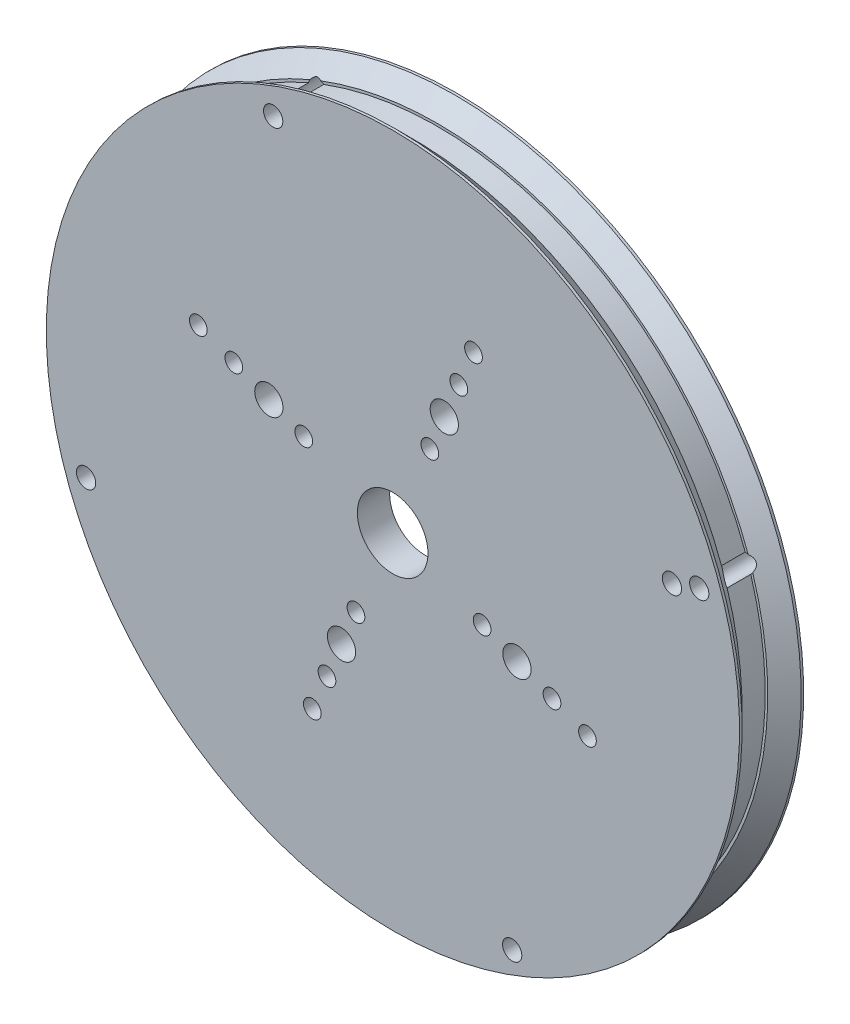
SolidWorks part; units mm, degrees
ref_plane "Plan de face" through (0, 0, 0) normal (0, 0, 1) x (1, 0, 0)
ref_plane "Plan de dessus" through (0, 0, 0) normal (0, 1, 0) x (1, 0, 0)
ref_plane "Plan de droite" through (0, 0, 0) normal (1, 0, 0) x (0, 0, -1)
sketch "Esquisse1" plane through (0, 0, 1.6866) normal (1, 0, 0) x (0, 0, -1)
  line L1 (0.1714, -3) -> (-1.8286, -3)
  line L2 (0.1714, -3) -> (0.1714, 22.5)
  line L3 (0.1714, 22.5) -> (-1.8286, 22.5)
  line L4 (-1.8286, -3) -> (-1.8286, 22.5)
  line L13 (1.6714, -3) -> (0.1714, -3)
  line L14 (1.6714, -3) -> (1.6714, 24)
  line L15 (1.6714, 24) -> (0.1714, 24)
  line L16 (0.1714, -3) -> (0.1714, 24)
  line L17 (-1.8286, 24) -> (-3.3286, 24)
  line L18 (-1.8286, 24) -> (-1.8286, -3)
  line L19 (-1.8286, -3) -> (-3.3286, -3)
  line L20 (-3.3286, 24) -> (-3.3286, -3)
  dimension "D1" = 1.5
  dimension "D2" = 1.5
  dimension "D3" = 2
  dimension "D4" = 25.5
  dimension "D5" = 27
revolve "Révolution1" add sketch "Esquisse1" angle 360 about L1 region at (0, 9.75, 2.5152) region at (0, 10.5, 0.7652) region at (0, 10.5, 4.2652)
sketch "Esquisse2" plane through (0, 0, 5.0152) normal (0, 0, 1) x (1, 0, 0)
  line L0 (26.9976, -3.3576) -> (-27, -2.9934) construction
  circle A0 centre (-0.0182, -3.1754) radius 2.75
  circle A1 centre (0, -3) radius 27 construction
extrude "Enlèv. mat.-Extru.1" cut sketch "Esquisse2" against normal blind 10
sketch "Esquisse13" plane through (0, 0, 0) normal (0, 0, 1) x (1, 0, 0)
  line L0 (-122.2352, 39.9508) -> (-38.6976, 41.258) construction
  line L1 (-36.0992, -44.5996) -> (67.3726, -4.8805) construction
  line L4 (15.1562, -9.278) -> (-15.1562, 3.278) construction
  line L5 (-6.278, -18.1562) -> (6.278, 12.1562) construction
  circle A2 centre (-2.8778, -9.9476) radius 0.6896
  circle A3 centre (6.9476, -5.8778) radius 0.6896
  circle A4 centre (9.6638, -7.0029) radius 1.1
  circle A5 centre (12.3938, -8.1338) radius 0.6896
  circle A6 centre (15.1562, -9.278) radius 0.6896
  circle A7 centre (2.8778, 3.9476) radius 0.6896
  circle A8 centre (4.0029, 6.6638) radius 1.1
  circle A9 centre (5.1338, 9.3938) radius 0.6896
  circle A10 centre (6.278, 12.1562) radius 0.6896
  circle A11 centre (-4.0029, -12.6638) radius 1.1
  circle A12 centre (-5.1338, -15.3938) radius 0.6896
  circle A13 centre (-6.278, -18.1562) radius 0.6896
  circle A14 centre (-6.9476, -0.1222) radius 0.6896
  circle A15 centre (-9.6638, 1.0029) radius 1.1
  circle A16 centre (-12.3938, 2.1338) radius 0.6896
  circle A17 centre (-15.1562, 3.278) radius 0.6896
  circle A19 centre (0, -3) radius 7.52 construction
  circle A20 centre (0, -3) radius 10.46 construction
  circle A21 centre (0, -3) radius 13.415 construction
  circle A22 centre (0, -3) radius 16.405 construction
sketch "Esquisse14" plane through (0, 0, 0) normal (0, 0, 1) x (1, 0, 0)
  line L0 (-122.2352, 39.9508) -> (-38.6976, 41.258) construction
  line L1 (-36.0992, -44.5996) -> (67.3726, -4.8805) construction
  spline S0 degree 2 poles (6.7095, 2.7436) (4.5975, -1.3195) (9.1051, -2.6286) knots 0 0 0 1 1 1 construction
  spline S1 degree 3 poles (-0.5608, 5.6062) (1.1805, 8.2527) (2.8687, 10.4384) (5.1281, 13.8669) (7.0874, 14.3139) (8.3916, 12.6802) (7.2661, 8.5047) (7.0552, 4.6338) (6.7095, 2.7436) knots 0 0 0 0 0.368171 0.418118 0.499474 0.581227 0.63128 1 1 1 1 construction
  spline S2 degree 2 poles (-0.5608, 5.6062) (-1.8662, 1.4438) (-5.8382, 3.5619) knots 0 0 0 1 1 1 construction
  spline S3 degree 3 poles (9.1051, -2.6286) (11.376, -4.297) (13.9367, -6.0338) (16.9471, -8.1818) (17.3829, -10.0409) (15.6763, -11.2158) (11.6017, -10.1948) (8.3971, -9.8909) (5.7682, -9.4912) knots 0 0 0 0 0.365231 0.41369 0.484595 0.573039 0.62458 1 1 1 1 construction
  spline S4 degree 2 poles (5.7682, -9.4912) (2.1673, -7.506) (0.914, -11.3287) knots 0 0 0 1 1 1 construction
  spline S5 degree 3 poles (0.914, -11.3287) (-1.3562, -14.5677) (-2.4297, -16.1534) (-4.9925, -19.7972) (-7.106, -20.4883) (-8.0922, -18.5459) (-7.4183, -14.316) (-7.0267, -12.3758) (-6.3958, -8.7367) knots 0 0 0 0 0.370191 0.421117 0.509255 0.593778 0.642852 1 1 1 1 construction
  spline S6 degree 2 poles (-6.3958, -8.7367) (-4.4116, -4.9383) (-8.4827, -3.685) knots 0 0 0 1 1 1 construction
  spline S7 degree 3 poles (-8.4827, -3.685) (-11.9491, -1.3363) (-13.5133, -0.3098) (-16.9826, 2.3011) (-16.9406, 4.3561) (-15.2444, 5.1901) (-10.9497, 4.5175) (-8.5569, 4.0332) (-5.8382, 3.5619) knots 0 0 0 0 0.388588 0.439956 0.513686 0.605056 0.653688 1 1 1 1 construction
  spline S8 degree 1 poles (-0.8345, 5.7361) (-5.7395, 3.8493) knots 0 0 1 1 construction
  spline S9 degree 1 poles (-8.6139, -3.9586) (-5.7395, 3.8493) knots 0 0 1 1 construction
  spline S10 degree 1 poles (-6.6834, -8.6393) (-8.6139, -3.9586) knots 0 0 1 1 construction
  spline S11 degree 1 poles (1.1852, -11.4645) (-6.6834, -8.6393) knots 0 0 1 1 construction
  spline S12 degree 1 poles (5.6702, -9.7797) (1.1852, -11.4645) knots 0 0 1 1 construction
  spline S13 degree 1 poles (9.2399, -2.3554) (5.6702, -9.7797) knots 0 0 1 1 construction
  spline S14 degree 1 poles (6.9965, 2.6453) (9.2399, -2.3554) knots 0 0 1 1 construction
  spline S15 degree 1 poles (-0.8345, 5.7361) (6.9965, 2.6453) knots 0 0 1 1 construction
  spline S16 degree 2 poles (-0.8345, 5.7361) (-1.3236, 4.2068) (-2.6043, 3.2067) (-4.2666, 3.072) (-5.7395, 3.8493) knots -0.004811 -0.004811 -0.004811 0.373998 0.626538 1.005348 1.005348 1.005348
  spline S17 degree 3 poles (-5.7395, 3.8493) (-6.2151, 3.9317) (-7.1851, 4.1035) (-8.5214, 4.3474) (-9.8525, 4.5913) (-11.2133, 4.8349) (-12.4217, 5.0437) (-13.4517, 5.2099) (-14.2791, 5.3495) (-15.1763, 5.3548) (-16.0151, 5.0974) (-16.7156, 4.5962) (-17.1548, 3.816) (-17.2469, 2.9159) (-16.9724, 2.0275) (-16.3347, 1.4225) (-15.7222, 0.9845) (-15.1601, 0.5645) (-14.4443, 0.0444) (-13.597, -0.5611) (-12.5732, -1.2728) (-11.4658, -2.0289) (-10.3988, -2.7508) (-9.435, -3.4026) (-8.8816, -3.7772) (-8.6139, -3.9586) knots -0.001388 -0.001388 -0.001388 -0.001388 0.061325 0.124038 0.18675 0.249463 0.312175 0.343532 0.374888 0.406244 0.437601 0.468957 0.500313 0.53167 0.563026 0.594382 0.625739 0.657095 0.688451 0.751164 0.813876 0.876589 0.939302 0.970658 1.002014 1.002014 1.002014 1.002014
  spline S18 degree 2 poles (-8.6139, -3.9586) (-7.1152, -4.4284) (-6.1191, -5.6542) (-5.9577, -7.2336) (-6.6834, -8.6393) knots -0.005465 -0.005465 -0.005465 0.373559 0.626242 1.005266 1.005266 1.005266
  spline S19 degree 3 poles (-6.6834, -8.6393) (-6.7365, -8.9456) (-6.8467, -9.5773) (-7.0427, -10.6867) (-7.2659, -11.9301) (-7.5064, -13.2594) (-7.7338, -14.5378) (-7.9261, -15.6428) (-8.082, -16.6025) (-8.2179, -17.3704) (-8.2866, -18.2563) (-8.0649, -19.167) (-7.5956, -19.9388) (-6.8052, -20.4093) (-5.903, -20.3614) (-5.0536, -20.0041) (-4.3484, -19.3959) (-3.7001, -18.4845) (-3.0206, -17.5077) (-2.2697, -16.4295) (-1.5425, -15.3799) (-0.7725, -14.2696) (-0.0397, -13.2162) (0.6214, -12.2695) (1.0012, -11.727) (1.1852, -11.4645) knots -0.001388 -0.001388 -0.001388 -0.001388 0.029952 0.061293 0.123974 0.186655 0.249336 0.312017 0.343358 0.374698 0.406039 0.43738 0.46872 0.500061 0.531401 0.562742 0.594082 0.625423 0.688104 0.750785 0.813466 0.876147 0.938829 0.970169 1.00151 1.00151 1.00151 1.00151
  spline S20 degree 2 poles (1.1852, -11.4645) (1.6549, -10.0593) (2.8294, -9.1584) (4.3345, -9.0507) (5.6702, -9.7797) knots -0.006505 -0.006505 -0.006505 0.373008 0.626017 1.005531 1.005531 1.005531
  spline S21 degree 3 poles (5.6702, -9.7797) (6.5695, -9.9164) (7.9012, -10.0932) (9.7591, -10.3475) (11.1725, -10.5612) (12.369, -10.7706) (13.3391, -10.9668) (14.0651, -11.124) (14.8219, -11.319) (15.7086, -11.3124) (16.5342, -10.937) (17.1821, -10.3101) (17.4648, -9.4297) (17.3189, -8.5471) (16.8686, -7.7861) (16.2466, -7.3076) (15.6668, -6.9045) (14.8845, -6.3515) (13.9112, -5.6724) (12.7425, -4.8563) (11.1877, -3.7652) (10.0127, -2.9232) (9.2399, -2.3554) knots -0.002298 -0.002298 -0.002298 -0.002298 0.123304 0.186105 0.248906 0.311707 0.343107 0.374508 0.405908 0.437309 0.468709 0.50011 0.53151 0.562911 0.594311 0.625712 0.657112 0.688513 0.751314 0.814115 0.876916 1.002518 1.002518 1.002518 1.002518
  spline S22 degree 2 poles (9.2399, -2.3554) (7.5706, -1.8635) (6.4345, -0.548) (6.2248, 1.1415) (6.9965, 2.6453) knots -0.004925 -0.004925 -0.004925 0.374047 0.626695 1.005666 1.005666 1.005666
  spline S23 degree 3 poles (6.9965, 2.6453) (7.028, 2.8173) (7.0839, 3.1488) (7.1937, 3.9233) (7.3237, 5.0061) (7.494, 6.4638) (7.6993, 8.0218) (7.9171, 9.3576) (8.1305, 10.428) (8.3105, 11.208) (8.5229, 12.0338) (8.3984, 12.963) (7.885, 13.7297) (6.857, 14.4307) (5.5694, 14.3145) (4.6084, 13.6014) (4.1464, 12.9286) (3.7376, 12.3158) (3.1863, 11.5143) (2.5114, 10.5517) (1.703, 9.4162) (0.8836, 8.2606) (0.0505, 7.0631) (-0.5468, 6.1733) (-0.8345, 5.7361) knots -0.001626 -0.001626 -0.001626 -0.001626 0.029765 0.061156 0.123938 0.18672 0.249502 0.312284 0.343675 0.375066 0.406457 0.437848 0.469239 0.50063 0.563412 0.594802 0.626193 0.657584 0.688975 0.751757 0.814539 0.877321 0.940103 1.002885 1.002885 1.002885 1.002885
  dimension "D1" = 0.3
extrude "Enlèv. mat.-Extru.4" cut sketch "Esquisse13" along normal blind 10
extrude "Enlèv. mat.-Extru.5" cut sketch "Esquisse14" along normal blind 2.5
sketch "Esquisse15" plane through (0, 0, 0.0152) normal (0, 0, -1) x (-1, 0, 0)
  line L0 (-23.8619, 5.0285) -> (23.8983, -11.3792) construction
  line L1 (9.3268, 20.2962) -> (-9.2904, -26.6469) construction
  circle A0 centre (-23.8619, 5.0285) radius 0.75
  circle A2 centre (23.8983, -11.3792) radius 0.75
  circle A3 centre (9.3268, 20.2962) radius 0.75
  circle A4 centre (-9.2904, -26.6469) radius 0.75
  circle A5 centre (0.0182, -3.1754) radius 25.25 construction
  circle A6 centre (0.0182, -3.1754) radius 23 construction
  circle A8 centre (-21.7339, 4.2974) radius 0.75
extrude "Enlèv. mat.-Extru.6" cut sketch "Esquisse15" against normal blind 6 contours A8 | A2 | A3 | A0 | A4 region at (21.7339, 4.2974, 0.0152)
chamfer "Chanfrein1" distance 1.3 angle 45 2 edges at (0, 24, 1.5152) (0, 24, 3.5152)
